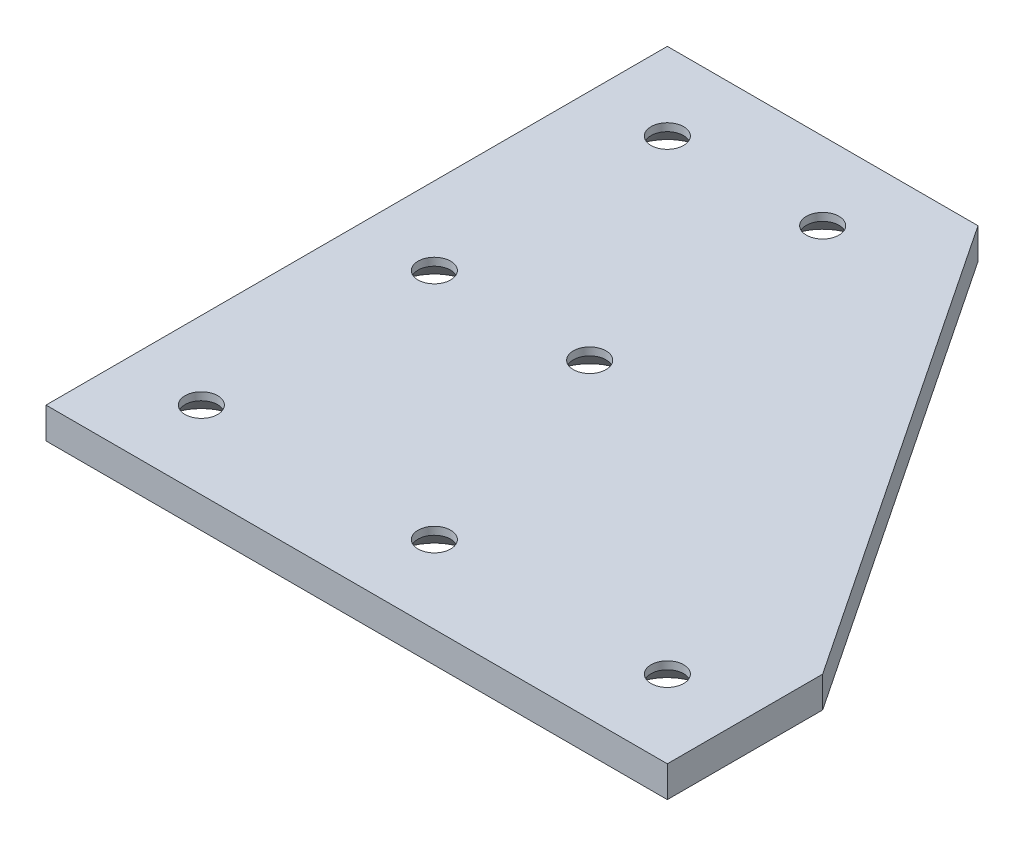
SolidWorks part; units mm, degrees
material "Aluminum 6105-T5"
ref_plane "Front Plane" through (0, 0, 0) normal (0, 0, 1) x (1, 0, 0)
ref_plane "Top Plane" through (0, 0, 0) normal (0, 1, 0) x (1, 0, 0)
ref_plane "Right Plane" through (0, 0, 0) normal (1, 0, 0) x (0, 0, -1)
sketch "Sketch1" plane through (0, 0, 0) normal (0, 1, 0) x (1, 0, 0)
  line L0 (0, 0) -> (80, 0)
  line L1 (80, 0) -> (80, 20)
  line L2 (80, 20) -> (40, 80)
  line L3 (40, 80) -> (0, 80)
  line L4 (0, 80) -> (0, 0)
  point P8 (0, 80)
  point P11 (40, 80)
  point P14 (80, 20)
  point P17 (80, 0)
  point P20 (0, 0)
  dimension "D1" = 80
  dimension "D2" = 80
  dimension "D3" = 20
  dimension "D4" = 40
extrude "Boss-Extrude1" add sketch "Sketch1" along normal blind 4
sketch "Sketch2" plane through (0, 4, 0) normal (0, 1, 0) x (1, 0, 0)
  line L0 (0, 0) -> (80, 0) construction
  line L1 (0, 80) -> (0, 0) construction
  line L2 (80, 0) -> (80, 20) construction
  line L3 (40, 80) -> (0, 80) construction
  circle A0 centre (10, 10) radius 2.1
  circle A1 centre (40, 10) radius 2.1
  circle A2 centre (70, 10) radius 2.1
  circle A4 centre (30, 40) radius 2.1
  circle A5 centre (30, 70) radius 2.1
  circle A6 centre (10, 40) radius 2.1
  circle A7 centre (10, 70) radius 2.1
  circle A8 centre (30, 10) radius 2.1 [skipped]
  dimension "D1" = 4.2
  dimension "D3" = 3
  dimension "D2" = 10
  dimension "10" = 10
  dimension "D4" = 10
  dimension "D7" = 10
  dimension "D8" = 10
  dimension "D9" = 20
  dimension "D5" = 2
  dimension "D6" = 3
extrude "Cut-Extrude1" cut sketch "Sketch2" against normal blind 4
chamfer "Chamfer1" distance 3 angle 45 7 edges at (10, 0, -67.9) (30, 0, -67.9) (30, 0, -37.9) (10, 0, -37.9) (10, 0, -7.9) (40, 0, -7.9) (70, 0, -7.9)
fillet "Fillet1" [suppressed] radius 1
